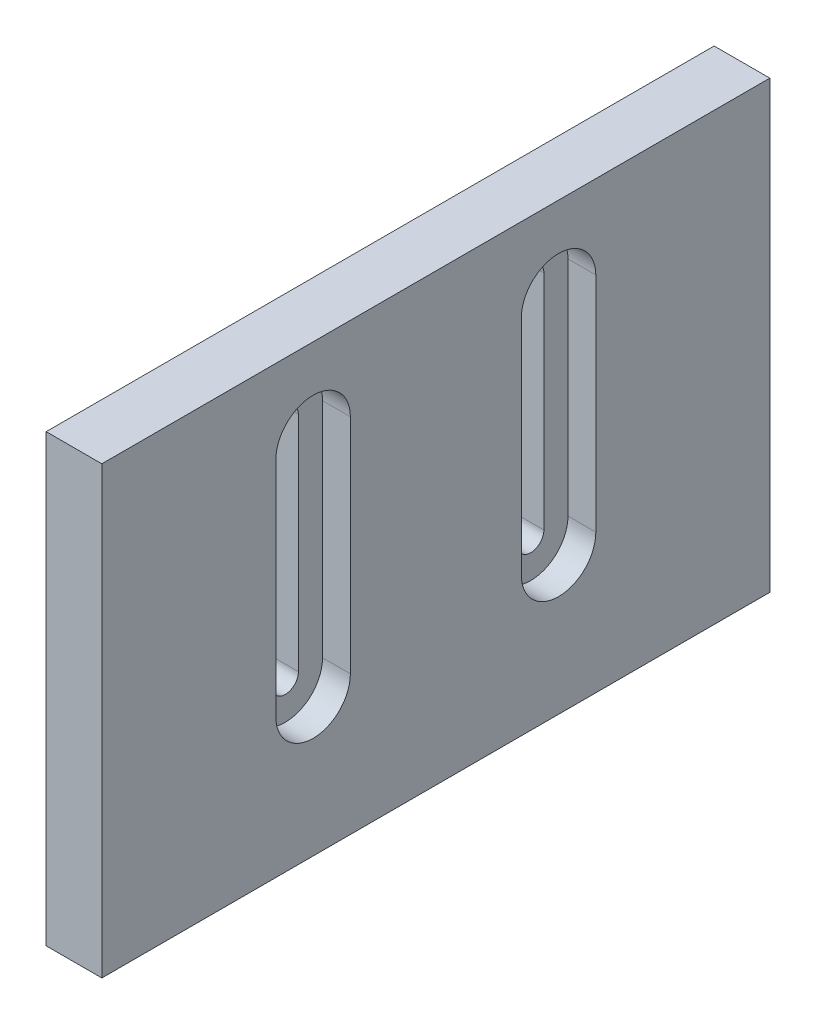
SolidWorks part; units mm, degrees
ref_plane "Front Plane" through (0, 0, 0) normal (0, 0, 1) x (1, 0, 0)
ref_plane "Top Plane" through (0, 0, 0) normal (0, 1, 0) x (1, 0, 0)
ref_plane "Right Plane" through (0, 0, 0) normal (1, 0, 0) x (0, 0, -1)
sketch "Sketch2" plane through (0, 0, 0) normal (1, 0, 0) x (0, 0, -1)
  line L1 (38.1, -25.4) -> (-38.1, -25.4)
  line L2 (38.1, -25.4) -> (38.1, 25.4)
  line L3 (38.1, 25.4) -> (-38.1, 25.4)
  line L4 (-38.1, -25.4) -> (-38.1, 25.4)
  line L5 (38.1, -25.4) -> (-38.1, 25.4) construction
  line L6 (38.1, 25.4) -> (-38.1, -25.4) construction
  dimension "D1" = 76.2
  dimension "D2" = 50.8
extrude "Boss-Extrude2" add sketch "Sketch2" along normal mid plane 6.35
sketch "Sketch3" plane through (3.175, 0, 0) normal (1, 0, 0) x (0, 0, -1)
  line L0 (-14, -9.525) -> (-14, 15.875) construction
  line L3 (-15.5, -9.525) -> (-15.5, 15.875)
  line L6 (-12.5, -9.525) -> (-12.5, 15.875)
  line L7 (14, -9.525) -> (14, 15.875) construction
  line L8 (12.5, -9.525) -> (12.5, 15.875)
  line L9 (15.5, -9.525) -> (15.5, 15.875)
  line L10 (38.1, 25.4) -> (-38.1, 25.4) construction
  line L11 (-18.25, -9.525) -> (-18.25, 15.875)
  line L12 (-9.75, -9.525) -> (-9.75, 15.875)
  line L13 (9.75, -9.525) -> (9.75, 15.875)
  line L14 (18.25, -9.525) -> (18.25, 15.875)
  line L15 (-14, 3.175) -> (14, 3.175) construction
  line L16 (0, 3.175) -> (0, 0) construction
  arc A4 (-15.5, -9.525) -> (-12.5, -9.525) centre (-14, -9.525) ccw
  arc A5 (-12.5, 15.875) -> (-15.5, 15.875) centre (-14, 15.875) ccw
  arc A6 (12.5, -9.525) -> (15.5, -9.525) centre (14, -9.525) ccw
  arc A7 (15.5, 15.875) -> (12.5, 15.875) centre (14, 15.875) ccw
  arc A8 (-9.75, 15.875) -> (-18.25, 15.875) centre (-14, 15.875) ccw
  arc A9 (-18.25, -9.525) -> (-9.75, -9.525) centre (-14, -9.525) ccw
  arc A10 (18.25, 15.875) -> (9.75, 15.875) centre (14, 15.875) ccw
  arc A11 (9.75, -9.525) -> (18.25, -9.525) centre (14, -9.525) ccw
  point P2 (-14, 3.175)
  point P7 (14, 3.175)
  dimension "D1" = 3
  dimension "D5" = 8.5
  dimension "D2" = 28
  dimension "D3" = 9.525
  dimension "D4" = 25.4
extrude "Cut-Extrude1" cut sketch "Sketch3" against normal through all both and the other way through all contours L6 A5 L3 A4 | L9 A7 L8 A6 region at (3.175, 3.175, 14) region at (3.175, 3.175, -14)
extrude "Cut-Extrude3" cut sketch "Sketch3<3>" against normal blind 3.175
sketch "Sketch3<3>" plane through (3.175, 0, 0) normal (1, 0, 0) x (0, 0, -1) same geometry as "Sketch3"
sketch "Sketch4" plane through (0, -25.4, 0) normal (0, -1, 0) x (1, 0, 0)
  circle A0 centre (0, 25.4) radius 1.27
  circle A2 centre (0, 0) radius 1.27
  circle A3 centre (0, -25.4) radius 1.27
  dimension "D1" = 2.54
  dimension "D2" = 25.4
extrude "Cut-Extrude2" cut sketch "Sketch4" against normal blind 15.24 and the other way through all
equation "\"D1@Sketch3\"=3mm"
equation "\"D5@Sketch3\"=8.5mm"
